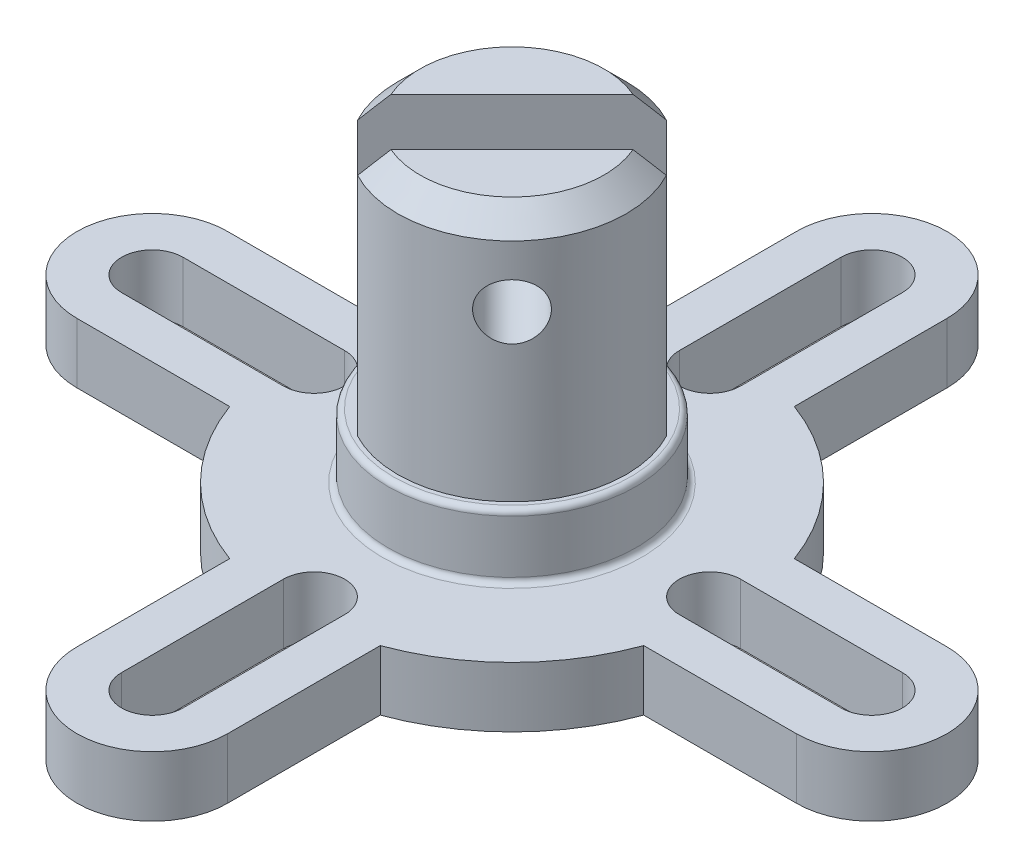
SolidWorks part; units mm, degrees
material "6061 Alloy"
ref_plane "Front" through (0, 0, 0) normal (0, 0, 1) x (1, 0, 0)
ref_plane "Top" through (0, 0, 0) normal (0, 1, 0) x (1, 0, 0)
ref_plane "Right" through (0, 0, 0) normal (1, 0, 0) x (0, 0, -1)
sketch "Sketch3" plane through (0, 0, 0) normal (0, 1, 0) x (1, 0, 0)
  circle A0 centre (0, 0) radius 10.033
  dimension "D1" = 20.066
extrude "Boss-Extrude1" add sketch "Sketch3" along normal blind 2.7432
sketch "Sketch4" plane through (0, 2.7432, 0) normal (0, 1, 0) x (1, 0, 0)
  line L0 (9.017, 0) -> (16.383, 0) construction
  line L1 (9.017, 1.397) -> (16.383, 1.397)
  line L2 (9.017, -1.397) -> (16.383, -1.397)
  line L3 (9.017, 3.429) -> (16.383, 3.429)
  line L4 (9.017, -3.429) -> (16.383, -3.429)
  line L5 (9.4288, -3.429) -> (9.017, -3.429)
  line L6 (9.4288, 3.429) -> (9.017, 3.429)
  arc A0 (9.017, 1.397) -> (9.017, -1.397) centre (9.017, 0) ccw
  arc A1 (16.383, -1.397) -> (16.383, 1.397) centre (16.383, 0) ccw
  arc A2 (16.383, -3.429) -> (16.383, 3.429) centre (16.383, 0) ccw
  circle A3 centre (0, 0) radius 10.033 construction
  arc A4 (9.017, 3.429) -> (9.017, -3.429) centre (9.017, 0) ccw construction
  point P3 (12.7, 0)
  point P8 (17.78, 0)
  point P9 (7.62, 0)
  circle M3 centre (0, 0) radius 10.033
  dimension "D1" = 2.794
  dimension "D2" = 17.78
  dimension "D3" = 10.16
  dimension "D4" = 2.032
extrude "Boss-Extrude2" add sketch "Sketch4" against normal up to surface (2.7432 mm away) contours L4 A2 L3 L6 A0 L1 A1 L2 L5 M3 region at (9.856, 2.7432, -2.4563) up to face at (0, 0, 10.033)
extrude "Cut-Extrude1" cut sketch "Sketch4<3>" against normal up to next contours L1 A0 L2 M3 region at (8.937, 2.7432, 0)
sketch "Sketch4<3>" plane through (0, 2.7432, 0) normal (0, 1, 0) x (1, 0, 0) same geometry as "Sketch4"
pattern_circular "CirPattern1" count 4 over 360 about axis through (0, 2.7432, 0) along (0, 1, 0) of "Boss-Extrude2", "Cut-Extrude1"
sketch "Sketch5" plane through (0, 2.7432, 0) normal (0, 1, 0) x (1, 0, 0)
  circle A0 centre (0, 0) radius 5.6515
  dimension "D1" = 11.303
extrude "Boss-Extrude3" add sketch "Sketch5" along normal blind 2.921
sketch "Sketch6" plane through (0, 5.6642, 0) normal (0, 1, 0) x (1, 0, 0)
  line L0 (0, 0) -> (0, 5.207) construction
  line L1 (0, 0) -> (3.6819, 3.6819) construction
  line L2 (4.6076, 2.4254) -> (-2.4254, -4.6076)
  line L3 (2.4254, 4.6076) -> (-4.6076, -2.4254)
  circle A0 centre (0, 0) radius 5.207
  point P7 (1.841, 1.841)
  dimension "D1" = 10.414
  dimension "D2" = 45
  dimension "D3" = 1.5431
extrude "Boss-Extrude4" add sketch "Sketch6" along normal offset from surface (11.303 mm away) 14.224 contours L2 A0 | L3 A0 region at (2.1668, 5.6642, 2.1668) region at (-2.1668, 5.6642, -2.1668) up to face at (0, 2.7432, 5.6515) offset beyond the face yes
chamfer "Chamfer1" distance 1.016 angle 45 2 edges at (-3.6819, 16.9672, -3.6819) (3.6819, 16.9672, 3.6819)
fillet "Fillet1" radius 0.254 2 edges at (0, 5.6642, 5.6515) (0, 2.7432, 5.6515)
sketch "Sketch7" plane through (-1.0911, 0, -1.0911) normal (0.7071, 0, 0.7071) x (0.7071, 0, -0.7071)
  line L1 (3.8966, 16.9672) -> (-3.8966, 16.9672) construction
  circle A0 centre (0, 13.1572) radius 1.27
  dimension "D1" = 2.54
  dimension "D2" = 3.81
extrude "Cut-Extrude2" cut sketch "Sketch7" against normal up to next and the other way up to next
ref_plane "Mating Plane" through (1.0911, 16.9672, 1.0911) normal (-0.7071, 0, 0.7071) x (0.7071, 0, 0.7071)
